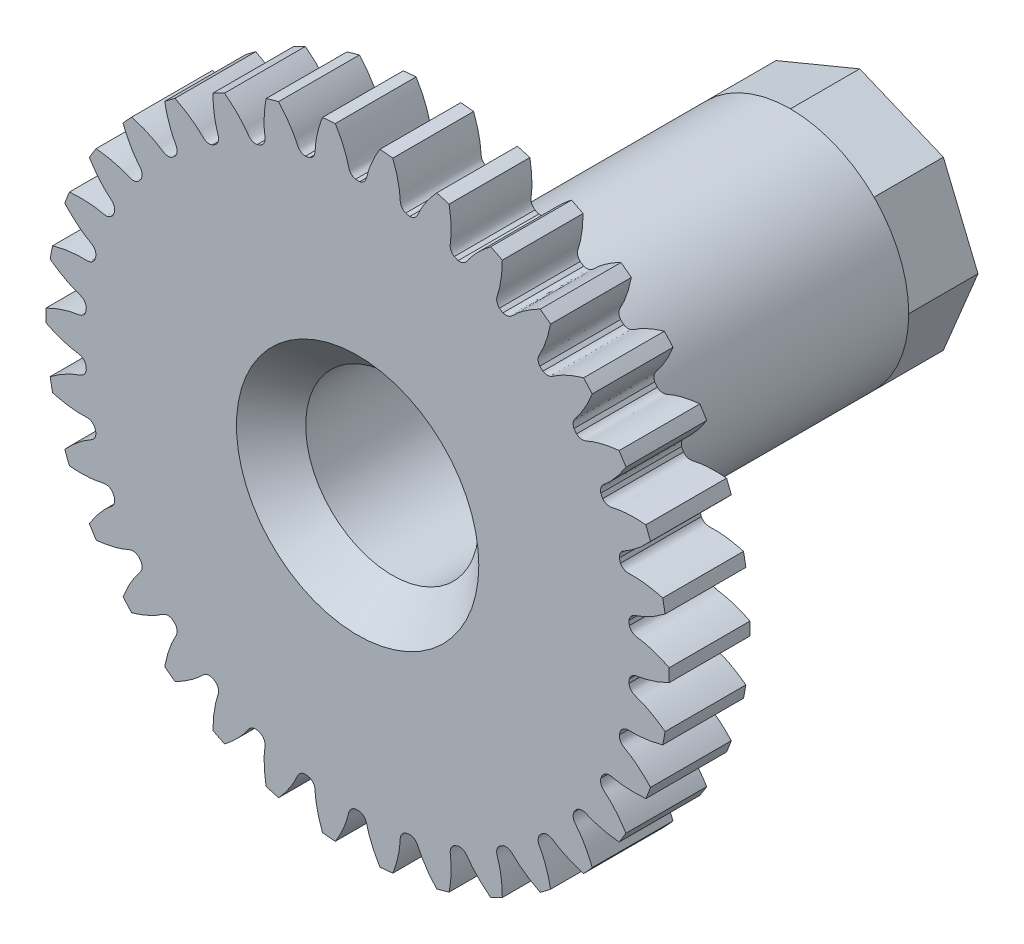
SolidWorks part; units mm, degrees
material "ABS"
ref_plane "前视基准面" through (0, 0, 0) normal (0, 0, 1) x (1, 0, 0)
ref_plane "上视基准面" through (0, 0, 0) normal (0, 1, 0) x (1, 0, 0)
ref_plane "右视基准面" through (0, 0, 0) normal (1, 0, 0) x (0, 0, -1)
sketch "草图1" plane through (0, 0, 0) normal (0, 0, 1) x (1, 0, 0)
  circle A0 centre (0, 0) radius 27
extrude "凸台-拉伸1" add sketch "草图1" along normal blind 7
ref_axis "基准轴1" through (0, 0, -1.5) along (0, 0, 1)
sketch "草图2" plane through (0, 0, 0) normal (0, 0, 1) x (1, 0, 0)
  line L0 (0, 0) -> (0, 27) construction
  circle A0 centre (0, 0) radius 27 construction
  arc A1 (0.1832, 23.6243) -> (-0.1832, 23.6243) centre (0, 0) ccw
  arc A2 (5.0574, 30.5549) -> (-5.0574, 30.5549) centre (0, 0) ccw
  spline S0 degree 3 poles (0.1832, 23.6243) (0.7166, 23.7751) (0.7634, 24.1888) (0.8799, 24.6236) (0.9129, 24.7382) (0.9511, 24.8613) (0.9947, 24.9927) (1.0441, 25.1322) (1.0997, 25.2797) (1.1618, 25.4349) (1.2307, 25.5977) (1.3068, 25.7679) (1.3903, 25.9451) (1.4816, 26.1292) (1.581, 26.32) (1.6888, 26.5172) (1.8053, 26.7204) (1.9308, 26.9296) (2.0655, 27.1443) (2.2097, 27.3642) (2.3637, 27.5892) (2.5278, 27.8188) (2.7021, 28.0528) (2.887, 28.2909) (3.0826, 28.5326) (3.2892, 28.7777) (3.5069, 29.0258) (3.7361, 29.2767) (3.9768, 29.5298) (4.2293, 29.7848) (4.5864, 30.1315) (4.8656, 30.3865) (5.0574, 30.5549) knots 0 0 0 0 0.130724 0.143504 0.157401 0.172415 0.188546 0.205794 0.224159 0.243641 0.26424 0.285956 0.308788 0.332738 0.357805 0.383988 0.411289 0.439706 0.46924 0.499892 0.53166 0.564545 0.598547 0.633666 0.669902 0.707255 0.745725 0.785312 0.826016 0.867836 0.910774 1 1 1 1
  spline S1 degree 3 poles (-0.1832, 23.6243) (-0.7166, 23.7751) (-0.7634, 24.1888) (-0.8799, 24.6236) (-0.9129, 24.7382) (-0.9511, 24.8613) (-0.9947, 24.9927) (-1.0441, 25.1322) (-1.0997, 25.2797) (-1.1618, 25.4349) (-1.2307, 25.5977) (-1.3068, 25.7679) (-1.3903, 25.9451) (-1.4816, 26.1292) (-1.581, 26.32) (-1.6888, 26.5172) (-1.8053, 26.7204) (-1.9308, 26.9296) (-2.0655, 27.1443) (-2.2097, 27.3642) (-2.3637, 27.5892) (-2.5278, 27.8188) (-2.7021, 28.0528) (-2.887, 28.2909) (-3.0826, 28.5326) (-3.2892, 28.7777) (-3.5069, 29.0258) (-3.7361, 29.2767) (-3.9768, 29.5298) (-4.2293, 29.7848) (-4.5864, 30.1315) (-4.8656, 30.3865) (-5.0574, 30.5549) knots 0 0 0 0 0.130724 0.143504 0.157401 0.172415 0.188546 0.205794 0.224159 0.243641 0.26424 0.285956 0.308788 0.332738 0.357805 0.383988 0.411289 0.439706 0.46924 0.499892 0.53166 0.564545 0.598547 0.633666 0.669902 0.707255 0.745725 0.785312 0.826016 0.867836 0.910774 1 1 1 1
extrude "切除-拉伸1" cut sketch "草图2" along normal through all
pattern_circular "阵列(圆周)1" count 34 every 10.588 about axis through (0, 0, -1.5) along (0, 0, 1) of "切除-拉伸1"
sketch "草图3" plane through (0, 0, 0) normal (0, 0, 1) x (1, 0, 0)
  circle A0 centre (0, 0) radius 25.5 construction
  dimension "Dn" = 51
sketch "草图5" plane through (0, 0, 7) normal (0, 0, 1) x (1, 0, 0)
  circle A0 centre (0, 0) radius 21
  dimension "D1" = 42
extrude "凸台-拉伸2" add sketch "草图5" against normal blind 1 from surface starting at face at (0, 0, 0)
sketch "草图4" plane through (0, 0, 7) normal (0, 0, 1) x (1, 0, 0)
  circle A0 centre (0, 0) radius 7.5
  dimension "D1" = 15
extrude "切除-拉伸2" cut sketch "草图4" against normal through all
chamfer "倒角1" distance 3 angle 45 1 edges at (7.5, 0, 7)
sketch "草图6" plane through (0, 0, 7) normal (0, 0, 1) x (1, 0, 0)
  circle A0 centre (0, 0) radius 7.5
  circle A1 centre (0, 0) radius 10.25
  dimension "D1" = 15
  dimension "D2" = 20.5
extrude "凸台-拉伸3" add sketch "草图6" against normal blind 35.5 from surface starting at face at (7.5, 0, -1)
fillet "圆角1" radius 3 1 edges at (10.25, 0, -1) profile chamfer
sketch "草图7" plane through (0, 0, -36.5) normal (0, 0, -1) x (-1, 0, 0)
  line L0 (0, 10.25) -> (-7.2478, 7.2478)
  line L1 (-7.2478, 7.2478) -> (-10.25, 0)
  line L2 (-10.25, 0) -> (-7.2478, -7.2478)
  line L3 (-7.2478, -7.2478) -> (0, -10.25)
  line L4 (0, -10.25) -> (7.2478, -7.2478)
  line L5 (7.2478, -7.2478) -> (10.25, 0)
  line L6 (10.25, 0) -> (7.2478, 7.2478)
  line L7 (7.2478, 7.2478) -> (0, 10.25)
  circle A0 centre (0, 0) radius 10.25 construction
  circle A1 centre (0, 0) radius 10.25 construction
extrude "切除-拉伸3" cut sketch "草图7" against normal blind 6 flip side to cut
